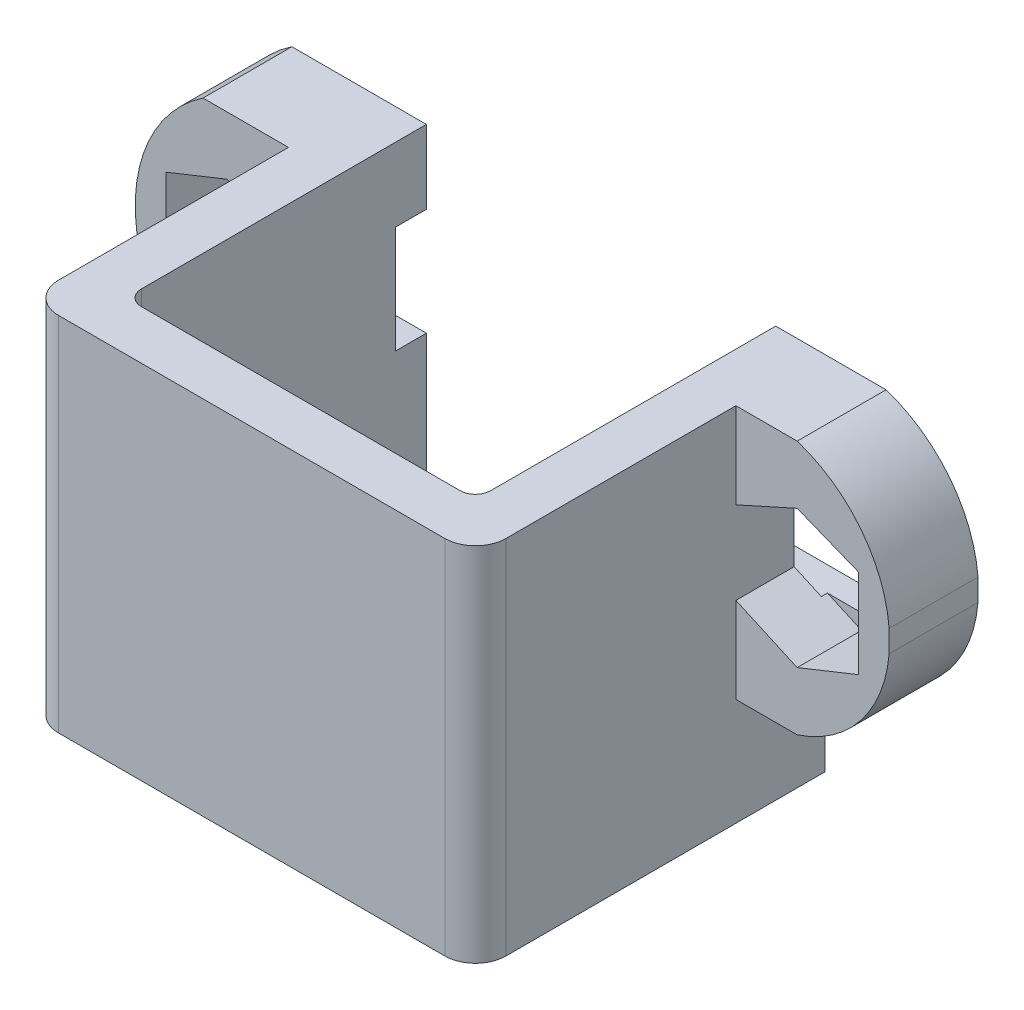
SolidWorks part; units mm, degrees
ref_plane "前视基准面" through (0, 0, 0) normal (0, 0, 1) x (1, 0, 0)
ref_plane "上视基准面" through (0, 0, 0) normal (0, 1, 0) x (1, 0, 0)
ref_plane "右视基准面" through (0, 0, 0) normal (1, 0, 0) x (0, 0, -1)
ref_plane "基准面1" through (0, 0, 1.6) normal (0, 0, 1) x (1, 0, 0)
sketch "草图1" plane through (0, 0, 1.6) normal (0, 0, 1) x (1, 0, 0)
  line L0 (-7.8, 0) -> (-10.8, 0)
  line L1 (-10.8, 0) -> (-11.007, 0.0828)
  line L2 (-11.007, 0.0828) -> (-11.007, 2)
  line L3 (-9.507, 3.5) -> (-8.05, 3.5)
  line L4 (-8.05, 3.5) -> (-7.3, 3.2)
  line L5 (-7.3, 3.2) -> (-7.3, 0.2)
  line L6 (-7.3, 0.2) -> (-7.8, 0)
  line L7 (-10.0888, -2.4) -> (9.3, -2.4)
  line L8 (12.3, 1.3912) -> (12.3, 2.1088)
  line L9 (9.3, 5.9) -> (-10.0888, 5.9)
  line L10 (7.3, 0.4) -> (7.3, 3.1)
  line L11 (7.3, 3.1) -> (8.1889, 3.5)
  line L12 (8.1889, 3.5) -> (9.2069, 3.5)
  line L13 (9.2069, 0) -> (8.1889, 0)
  line L14 (8.1889, 0) -> (7.3, 0.4)
  arc A0 (-11.007, 2) -> (-9.507, 3.5) centre (-9.507, 2) cw
  arc A1 (-10.0888, 5.9) -> (-10.0888, -2.4) centre (-7.3, 1.75) ccw
  arc A2 (9.3, -2.4) -> (12.3, 1.3912) centre (7.951, 1.75) ccw
  arc A3 (12.3, 2.1088) -> (9.3, 5.9) centre (7.951, 1.75) ccw
  arc A4 (9.2069, 3.5) -> (11.0062, 1.75) centre (9.2069, 1.7) cw
  arc A5 (11.0062, 1.75) -> (9.2069, 0) centre (9.2069, 1.8) cw
extrude "凸台-拉伸1" add sketch "草图1" against normal blind 11.4
sketch "草图2" plane through (0, 0, -9.8) normal (0, 0, -1) x (-1, 0, 0)
  line L0 (-5.7, -2.4) -> (5.7, -2.4)
  line L1 (5.7, -2.4) -> (5.7, 5.9)
  line L2 (5.7, 5.9) -> (-5.7, 5.9)
  line L3 (-5.7, 5.9) -> (-5.7, -2.4)
extrude "切除-拉伸1" cut sketch "草图2" against normal blind 9.8
sketch "草图3" plane through (0, 0, 1.6) normal (0, 0, 1) x (1, 0, 0)
  line L0 (-7.8, 0) -> (-10.8, 0)
  line L1 (-10.8, 0) -> (-9.3, -0.6)
  line L2 (-9.3, -0.6) -> (-7.8, 0)
extrude "切除-拉伸2" cut sketch "草图3" against normal blind 10.6
sketch "草图4" plane through (0, 0, -9.8) normal (0, 0, -1) x (-1, 0, 0)
  line L0 (11.007, 0.0828) -> (10.8, 0)
  line L1 (10.8, 0) -> (11.007, 0)
  line L2 (11.007, 0) -> (11.007, 0.0828)
extrude "切除-拉伸3" cut sketch "草图4" against normal blind 0.8
sketch "草图5" plane through (0, 0, 1.6) normal (0, 0, 1) x (1, 0, 0)
  line L0 (-9.507, 3.5) -> (-8.05, 3.5)
  line L1 (-8.05, 3.5) -> (-7.3, 3.2)
  line L2 (-7.3, 3.2) -> (-7.3, 5.9)
  line L3 (-7.3, 5.9) -> (-10.0888, 5.9)
  line L4 (-10.0888, -2.4) -> (-7.3, -2.4)
  line L5 (-7.3, -2.4) -> (-7.3, 0.2)
  line L6 (-7.3, 0.2) -> (-9.3, -0.6)
  line L7 (-9.3, -0.6) -> (-11.007, 0.0828)
  line L8 (-11.007, 0.0828) -> (-11.007, 2)
  arc A0 (-10.0888, 5.9) -> (-10.0888, -2.4) centre (-7.3, 1.75) ccw
  arc A1 (-11.007, 2) -> (-9.507, 3.5) centre (-9.507, 2) cw
extrude "切除-拉伸4" cut sketch "草图5" against normal blind 8.5
sketch "草图6" plane through (0, 0, -9.8) normal (0, 0, -1) x (-1, 0, 0)
  line L0 (7.3, 3.2) -> (8.05, 3.5)
  line L1 (8.05, 3.5) -> (5.7, 3.5)
  line L2 (5.7, 3.5) -> (5.7, 0)
  line L3 (5.7, 0) -> (7.8, 0)
  line L4 (7.8, 0) -> (7.3, 0.2)
  line L5 (7.3, 0.2) -> (7.3, 3.2)
extrude "切除-拉伸5" cut sketch "草图6" against normal blind 0.8
sketch "草图7" plane through (0, 0, -6.9) normal (0, 0, 1) x (1, 0, 0)
  line L0 (-9.507, 3.5) -> (-8.05, 3.5)
  line L1 (-8.05, 3.5) -> (-9.3, 4)
  line L2 (-9.3, 4) -> (-11.3, 3.2)
  line L3 (-11.3, 3.2) -> (-11.3, 0.2)
  line L4 (-11.3, 0.2) -> (-11.007, 0.0828)
  line L5 (-11.007, 0.0828) -> (-11.007, 2)
  arc A0 (-11.007, 2) -> (-9.507, 3.5) centre (-9.507, 2) cw
extrude "切除-拉伸6" cut sketch "草图7" against normal blind 2.1
sketch "草图8" plane through (0, 0, -9) normal (0, 0, -1) x (-1, 0, 0)
  line L0 (7.3, 3.2) -> (8.05, 3.5)
  line L1 (8.05, 3.5) -> (5.7, 3.5)
  line L2 (5.7, 3.5) -> (5.7, 0)
  line L3 (5.7, 0) -> (7.8, 0)
  line L4 (7.8, 0) -> (7.3, 0.2)
  line L5 (7.3, 0.2) -> (7.3, 3.2)
extrude "切除-拉伸7" cut sketch "草图8" against normal blind 0.2
sketch "草图9" plane through (0, 0, -9.8) normal (0, 0, -1) x (-1, 0, 0)
  line L0 (-7.3, 0.4) -> (-8.1889, 0)
  line L1 (-8.1889, 0) -> (-5.7, 0)
  line L2 (-5.7, 0) -> (-5.7, 3.5)
  line L3 (-5.7, 3.5) -> (-8.1889, 3.5)
  line L4 (-8.1889, 3.5) -> (-7.3, 3.1)
  line L5 (-7.3, 3.1) -> (-7.3, 0.4)
extrude "切除-拉伸8" cut sketch "草图9" against normal blind 1
sketch "草图10" plane through (0, 0, 1.6) normal (0, 0, 1) x (1, 0, 0)
  line L0 (9.2069, 0) -> (8.1889, 0)
  line L1 (8.1889, 0) -> (7.3, 0.4)
  line L2 (7.3, 0.4) -> (7.3, -2.4)
  line L3 (7.3, -2.4) -> (9.3, -2.4)
  line L4 (12.3, 1.3912) -> (12.3, 2.1088)
  line L5 (9.3, 5.9) -> (7.3, 5.9)
  line L6 (7.3, 5.9) -> (7.3, 3.1)
  line L7 (7.3, 3.1) -> (8.1889, 3.5)
  line L8 (8.1889, 3.5) -> (9.2069, 3.5)
  arc A0 (9.3, -2.4) -> (12.3, 1.3912) centre (7.951, 1.75) ccw
  arc A1 (12.3, 2.1088) -> (9.3, 5.9) centre (7.951, 1.75) ccw
  arc A2 (9.2069, 3.5) -> (11.0062, 1.75) centre (9.2069, 1.7) cw
  arc A3 (11.0062, 1.75) -> (9.2069, 0) centre (9.2069, 1.8) cw
extrude "切除-拉伸9" cut sketch "草图10" against normal blind 8.5
sketch "草图11" plane through (0, 0, -6.9) normal (0, 0, 1) x (1, 0, 0)
  line L0 (9.2069, 0) -> (8.1889, 0)
  line L1 (8.1889, 0) -> (9.3, -0.5)
  line L2 (9.3, -0.5) -> (11.3, 0.3)
  line L3 (11.3, 0.3) -> (11.3, 3.2)
  line L4 (11.3, 3.2) -> (9.3, 4)
  line L5 (9.3, 4) -> (8.1889, 3.5)
  line L6 (8.1889, 3.5) -> (9.2069, 3.5)
  arc A0 (9.2069, 3.5) -> (11.0062, 1.75) centre (9.2069, 1.7) cw
  arc A1 (11.0062, 1.75) -> (9.2069, 0) centre (9.2069, 1.8) cw
extrude "切除-拉伸10" cut sketch "草图11" against normal blind 1.9
sketch "草图12" plane through (0, 0, -8.8) normal (0, 0, 1) x (1, 0, 0)
  line L0 (9.2069, 0) -> (8.1889, 0)
  line L1 (8.1889, 0) -> (9.3, -0.5)
  line L2 (9.3, -0.5) -> (11.3, 0.3)
  line L3 (11.3, 0.3) -> (11.3, 3.2)
  line L4 (11.3, 3.2) -> (9.3, 4)
  line L5 (9.3, 4) -> (8.1889, 3.5)
  line L6 (8.1889, 3.5) -> (9.2069, 3.5)
  arc A0 (9.2069, 3.5) -> (11.0062, 1.75) centre (9.2069, 1.7) cw
  arc A1 (11.0062, 1.75) -> (9.2069, 0) centre (9.2069, 1.8) cw
extrude "切除-拉伸11" cut sketch "草图12" against normal blind 0.2
sketch "草图13" plane through (0, -2.4, 0) normal (0, -1, 0) x (1, 0, 0)
  line L0 (-7.3, 1.6) -> (7.3, 1.6)
  line L1 (7.3, 1.6) -> (7.3, -9.8)
  line L2 (7.3, -9.8) -> (5.7, -9.8)
  line L3 (5.7, -9.8) -> (5.7, 0)
  line L4 (5.7, 0) -> (-5.7, 0)
  line L5 (-5.7, 0) -> (-5.7, -9.8)
  line L6 (-5.7, -9.8) -> (-7.3, -9.8)
  line L7 (-7.3, -9.8) -> (-7.3, 1.6)
extrude "凸台-拉伸2" add sketch "草图13" along normal blind 3.5
fillet "圆角1" radius 0.5 2 edges at (-5.7, 0, 0) (5.7, 0, 0) tangent propagation no
fillet "圆角2" radius 1 2 edges at (-7.3, 0, 1.6) (7.3, 0, 1.6) tangent propagation no
fillet "圆角3" radius 1.5 1 edges at (-11.007, 0, -9.4) tangent propagation no
